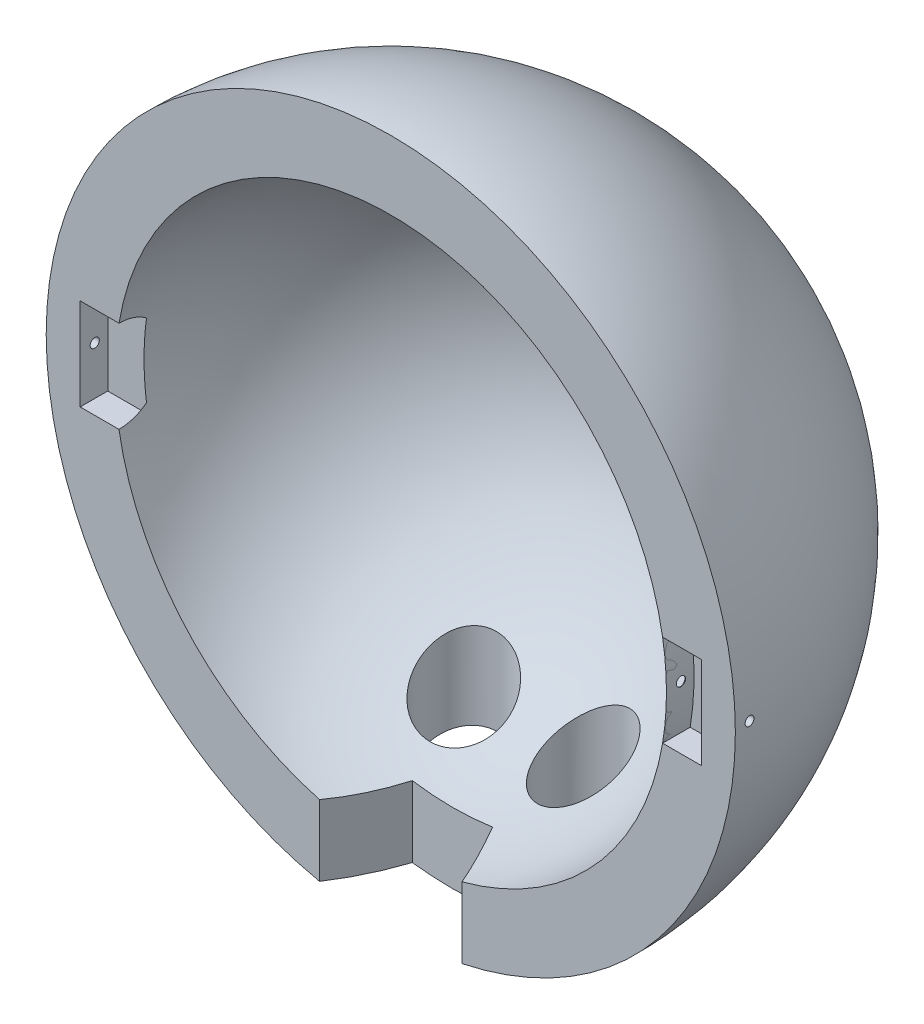
SolidWorks part; units mm, degrees
material "ABS"
ref_plane "Plano frontal" through (0, 0, 0) normal (0, 0, 1) x (1, 0, 0)
ref_plane "Plano superior" through (0, 0, 0) normal (0, 1, 0) x (1, 0, 0)
ref_plane "Plano direito" through (0, 0, 0) normal (1, 0, 0) x (0, 0, -1)
sketch "Esboço1" plane through (0, 0, 0) normal (0, 0, 1) x (1, 0, 0)
  line L0 (-60, 0) -> (-75, 0)
  line L1 (-60, 0) -> (-211.1575, 0) construction
  line L2 (75, 0) -> (60, 0)
  arc A0 (60, 0) -> (-60, 0) centre (0, 0) ccw
  arc A1 (75, 0) -> (-75, 0) centre (0, 0) ccw
  dimension "D1" = 120
  dimension "D2" = 150
revolve "Revolução1" add sketch "Esboço1" angle 180 about L1
sketch "Esboço3" plane through (0, 0, 0) normal (0, 0, 1) x (1, 0, 0)
  line L0 (0, 0) -> (75, 0) construction
  line L1 (0, 0) -> (67.6, 0) construction
  line L2 (0, 75) -> (0, 60) construction
  line L3 (-67.6, 0) -> (-67.6, -10)
  line L4 (60, 0) -> (75, 0) construction
  line L5 (67.6, 0) -> (59.1608, 0)
  line L6 (67.6, 0) -> (67.6, 10)
  line L7 (67.6, 10) -> (59.1608, 10)
  line L8 (75, 0) -> (60, 0) construction
  line L9 (59.1608, 0) -> (59.1608, 10)
  line L10 (67.6, 0) -> (59.1608, 0)
  line L11 (67.6, 0) -> (67.6, -10)
  line L12 (67.6, -10) -> (59.1608, -10)
  line L13 (59.1608, 0) -> (59.1608, -10)
  line L14 (-59.1608, 0) -> (-59.1608, -10)
  line L15 (-59.1608, 0) -> (-59.1608, 10)
  line L16 (-67.6, 0) -> (-67.6, 10)
  line L17 (-67.6, 10) -> (-59.1608, 10)
  line L18 (-67.6, -10) -> (-59.1608, -10)
  circle A0 centre (0, 0) radius 75 construction
  circle A1 centre (0, 0) radius 60 construction
  circle A2 centre (0, 0) radius 9.9527
  circle A3 centre (0, 0) radius 4.2943
  point P27 (0, 0)
  point P28 (0, 0)
  circle M1 centre (0, 0) radius 60
  dimension "D1" = 67.6
  dimension "D2" = 10
  dimension "D3" = 10
  dimension "D4" = 2
ref_axis "Eixo1" through (0, 0, -76.5762) along (0, 0, 1)
sketch "Esboço5" plane through (0, 0, 0) normal (0, 1, 0) x (1, 0, 0)
  circle A0 centre (-13, 28.8895) radius 8.75
  circle A1 centre (13, 28.8895) radius 8.75
  dimension "D1" = 17.5
  dimension "D2" = 17.5
  dimension "D3" = 13
  dimension "D4" = 26
extrude "Corte-extrusão2" cut sketch "Esboço5" against normal through all
sketch "Esboço6" plane through (0, 0, 0) normal (0, 1, 0) x (1, 0, 0)
  line L0 (0, 0) -> (15.5, 0)
  line L1 (15.5, 0) -> (8.6789, 13.5)
  line L2 (8.6789, 13.5) -> (-8.8211, 13.5)
  line L3 (-8.8211, 13.5) -> (-15.5, 0)
  line L4 (-75, 0) -> (75, 0) construction
  line L5 (-15.5, 0) -> (0, 0)
  dimension "D1" = 31
  dimension "D2" = 17.5
  dimension "D3" = 13.5
extrude "Corte-extrusão3" cut sketch "Esboço6" against normal through all
sketch "Esboço7" plane through (0, 0, 0) normal (0, 0, 1) x (1, 0, 0)
  circle A0 centre (0, 30) radius 10.9769
  dimension "D1" = 30
  dimension "D2" = 0
sketch "Esboço10" plane through (0, 0, 0) normal (0, 1, 0) x (1, 0, 0)
  line L0 (0, 0) -> (0, 7.2281) construction
  line L1 (-17.5, 72.9298) -> (17.5, 72.9298)
  line L7 (0, 0) -> (0, 72.9298) construction
  line L8 (-17.5, 72.9298) -> (-17.5, 82.9298)
  line L10 (17.5, 72.9298) -> (17.5, 82.9298)
  line L11 (17.5, 82.9298) -> (-17.5, 82.9298)
  arc A0 (75, 0) -> (-75, 0) centre (0, 0) ccw construction
  point P0 (0, 100)
  dimension "D1" = 35
  dimension "D2" = 10
extrude "Corte-extrusão5" cut sketch "Esboço10" against normal through all and the other way through all
extrude "Corte-extrusão6" cut sketch "Esboço7" against normal through all
sketch "Esboço12" plane through (0, 0, 0) normal (0, 0, 1) x (1, 0, 0)
  circle A0 centre (13.25, 0) radius 0.7
  circle A1 centre (-13.25, 0) radius 0.7
  circle A2 centre (0, 0) radius 17.5 construction
  dimension "D3" = 1.4
  dimension "D4" = 1.4
  dimension "D1" = 13.25
  dimension "D2" = 26.5
sketch "Esboço13" plane through (0, 0, -72.9298) normal (0, 0, -1) x (-1, 0, 0)
  circle A0 centre (0, 0) radius 2
  circle A1 centre (-8, 0) radius 1.25
  circle A2 centre (8, 0) radius 1.25
  dimension "D1" = 4
  dimension "D2" = 2.5
  dimension "D3" = 2.5
  dimension "D4" = 16
  dimension "D5" = 8
extrude "Corte-extrusão13" cut sketch "Esboço12" against normal blind 100 and the other way blind 10
extrude "Corte-extrusão14" cut sketch "Esboço13" against normal blind 100 and the other way blind 100
ref_plane "Plane1" through (0, 0, 0) normal (0, 0, 1) x (1, 0, 0)
sketch "Sketch1" plane through (0, 0, 0) normal (0, 0, 1) x (1, 0, 0)
  line L1 (-80.7425, 80.4943) -> (79.6848, 80.4943)
  line L2 (-80.7425, 80.4943) -> (-80.7425, -77.8174)
  line L3 (-80.7425, -77.8174) -> (79.6848, -77.8174)
  line L4 (79.6848, 80.4943) -> (79.6848, -77.8174)
ref_plane "Plane2" through (0, 0, 0) normal (0, 0, 1) x (1, 0, 0)
extrude "Cut-Extrude5" cut sketch "Esboço3" against normal blind 6 contours L12 L11 L5 M1 | L6 L7 L5 M1 | L3 L18 L17 L16 M1 | L17 L15 L14 L18 L3 L16 region at (-63.6566, 0, 0) region at (63.6566, -5.0886, 0) region at (63.6566, 5.0886, 0)
ref_plane "Plane3" through (-67.6, 0, 0) normal (1, 0, 0) x (0, 0, -1)
sketch "Sketch5" plane through (-67.6, 0, 0) normal (1, 0, 0) x (0, 0, -1)
  line L0 (0, -10) -> (6.3212, 10.9763) construction
  line L1 (6.3212, 10.9763) -> (0, 10.9763) construction
  line L2 (0, 10.9763) -> (6.3212, -10.9909) construction
  circle A0 centre (3.1606, 0.4882) radius 1
  dimension "D1" = 2
extrude "Cut-Extrude6" cut sketch "Sketch5" against normal blind 25 and the other way blind 166
